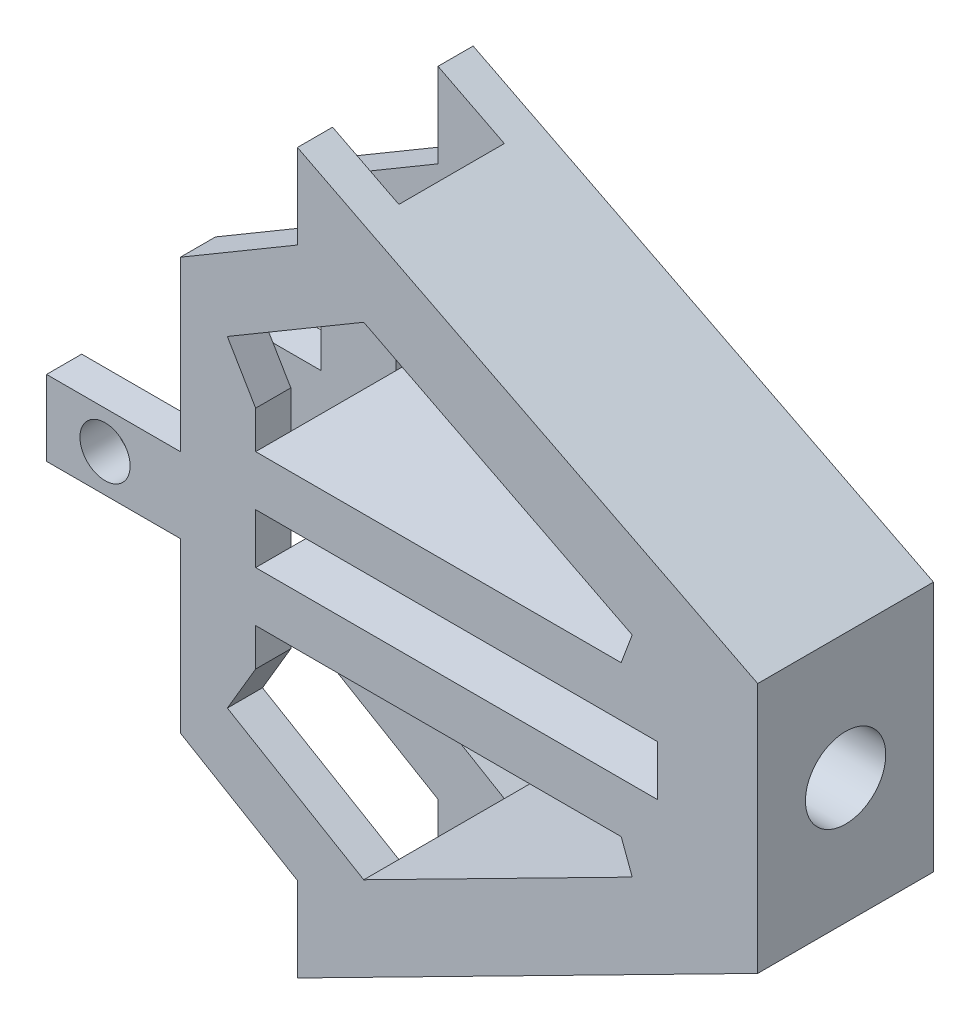
SolidWorks part; units mm, degrees
ref_plane "前视基准面" through (0, 0, 0) normal (0, 0, 1) x (1, 0, 0)
ref_plane "上视基准面" through (0, 0, 0) normal (0, 1, 0) x (1, 0, 0)
ref_plane "右视基准面" through (0, 0, 0) normal (1, 0, 0) x (0, 0, -1)
sketch "草图1" plane through (0, 0, 0) normal (0, 0, 1) x (1, 0, 0)
  line L12 (66, -1) -> (66, 1)
  line L13 (69, -5) -> (40, -19.75)
  line L14 (40, -19.75) -> (37, -19.75)
  line L15 (34.5, -16.75) -> (36.5, -16.75)
  line L16 (31, -16.75) -> (31, -19.75)
  line L17 (34, 13) -> (34, 2.5)
  line L18 (34, 13) -> (31, 16.75)
  line L19 (31, 19.75) -> (34, 19.75)
  line L20 (34, 19.75) -> (34, 17.25)
  line L21 (34.5, 16.75) -> (36.5, 16.75)
  line L22 (37, 13) -> (37, 1.5)
  line L23 (34, -19.75) -> (31, -19.75)
  line L24 (34, -13) -> (31, -16.75)
  line L25 (34, -19.75) -> (34, -17.25)
  line L26 (42.8383, -14.9406) -> (49, -4.5)
  line L27 (46, -1.5) -> (37, -1.5)
  line L28 (34, -2.5) -> (34, -13)
  line L29 (40, 14.6667) -> (46, 4.5)
  line L30 (46, 4.5) -> (46, 1.5)
  line L31 (63, 1.5) -> (64, 4.1774)
  line L32 (49, -1.5) -> (49, -4.5)
  line L33 (49, 4.5) -> (49, 1.5)
  line L34 (49, 1.5) -> (63, 1.5)
  line L35 (37, -17.25) -> (37, -19.75)
  line L36 (37, -1.5) -> (37, -13)
  line L37 (46, -1.5) -> (46, -4.5)
  line L38 (37, 19.75) -> (37, 17.25)
  line L39 (37, -13) -> (40, -14.6667)
  line L40 (46, -4.5) -> (40, -14.6667)
  line L41 (37, 13) -> (40, 14.6667)
  line L42 (37, 1.5) -> (46, 1.5)
  line L43 (42.8383, 14.9406) -> (64, 4.1774)
  line L44 (42.8383, -14.9406) -> (64, -4.1774)
  line L45 (49, 4.5) -> (42.8383, 14.9406)
  line L46 (66.5, 1.5) -> (69, 1.5)
  line L47 (69, 5) -> (69, 1.5)
  line L48 (63, -1.5) -> (49, -1.5)
  line L49 (37, 19.75) -> (40, 19.75)
  line L50 (40, 19.75) -> (69, 5)
  line L51 (31, 19.75) -> (31, 16.75)
  line L52 (69, -5) -> (69, -1.5)
  line L53 (66.5, -1.5) -> (69, -1.5)
  line L54 (63, -1.5) -> (64, -4.1774)
  line L55 (34, -2.5) -> (19.4926, -2.5)
  line L56 (34, 2.5) -> (19.4926, 2.5)
  line L57 (10, -13.9159) -> (19.4926, -2.5)
  line L58 (10, -19.75) -> (10, -13.9159)
  line L59 (10, -19.75) -> (7, -19.75)
  line L60 (7, -17.25) -> (7, -19.75)
  line L61 (3.5, -16.75) -> (6.5, -16.75)
  line L62 (3, -19.75) -> (3, -17.25)
  line L63 (3, -19.75) -> (0, -19.75)
  line L64 (3, -13.75) -> (7, -13.75)
  line L66 (18.0651, 0) -> (7, -13.75)
  line L67 (3, 13.75) -> (7, 13.75)
  line L68 (0, 19.75) -> (3, 19.75)
  line L69 (3, 19.75) -> (3, 17.25)
  line L70 (6.5, 16.75) -> (3.5, 16.75)
  line L71 (7, 19.75) -> (7, 17.25)
  line L72 (7, 19.75) -> (10, 19.75)
  line L73 (19.4926, 2.5) -> (10, 13.9159)
  line L74 (10, 19.75) -> (10, 13.9159)
  line L75 (7, 13.75) -> (18.0651, 0)
  line L78 (0, 19.75) -> (0, -19.75)
  line L81 (3, 13.75) -> (3, -13.75)
  arc A0 (66, -1) -> (66.5, -1.5) centre (66, -1.5) ccw
  arc A1 (37, -17.25) -> (36.5, -16.75) centre (37, -16.75) ccw
  arc A2 (34.5, -16.75) -> (34, -17.25) centre (34, -16.75) ccw
  arc A3 (34, 17.25) -> (34.5, 16.75) centre (34, 16.75) ccw
  arc A4 (36.5, 16.75) -> (37, 17.25) centre (37, 16.75) ccw
  arc A5 (66.5, 1.5) -> (66, 1) centre (66, 1.5) ccw
  arc A6 (7, -17.25) -> (6.5, -16.75) centre (7, -16.75) ccw
  arc A7 (3, 17.25) -> (3.5, 16.75) centre (3, 16.75) ccw
  arc A8 (6.5, 16.75) -> (7, 17.25) centre (7, 16.75) ccw
  arc A9 (3.5, -16.75) -> (3, -17.25) centre (3, -16.75) ccw
extrude "凸台-拉伸1" add sketch "草图1" along normal blind 4
sketch "草图2" plane through (0, -16.75, 0) normal (0, -1, 0) x (1, 0, 0)
  line L0 (3.5, 4) -> (6.5, 4) construction
  line L1 (3, 4) -> (3, 0) construction
  line L2 (7, 4) -> (7, 0) construction
  circle A0 centre (5, 2) radius 0.9
  dimension "D1" = 1.8
  dimension "D2" = 2
  dimension "D3" = 2
  dimension "D4" = 2
extrude "切除-拉伸1" cut sketch "草图2" against normal blind 52
sketch "草图3" plane through (0, 0, 4) normal (0, 0, 1) x (1, 0, 0)
  line L0 (3, 12.413) -> (3, 13.75)
  line L1 (3, 12.413) -> (0, 10.681)
  line L2 (0, 12.681) -> (0, 10.681)
  line L3 (0, 12.681) -> (3, 13.75)
  line L4 (24, -2.5) -> (24, 2.5)
  line L5 (24, -2.5) -> (22, -2.5)
  line L6 (22, 2.5) -> (22, -2.5)
  line L7 (22, 2.5) -> (24, 2.5)
  line L8 (3, -13.75) -> (3, -12.413)
  line L9 (3, -13.75) -> (0, -12.681)
  line L10 (0, -10.681) -> (0, -12.681)
  line L11 (0, -10.681) -> (3, -12.413)
extrude "凸台-拉伸2" add sketch "草图3" along normal blind 1.5
sketch "草图5" plane through (0, 0, 0) normal (0, 0, 1) x (1, 0, 0)
  line L0 (37, 7.25) -> (44.3771, 7.25)
  line L1 (37, 13) -> (37, 1.5) construction
  line L2 (46, 4.5) -> (40, 14.6667) construction
  line L3 (44.3771, 7.25) -> (50.664, 10.9603)
  line L4 (64, 4.1774) -> (42.8383, 14.9406) construction
  line L5 (37, 5.097) -> (45.6477, 5.097)
  line L6 (45.6477, 5.097) -> (53.3059, 9.6166)
  line L8 (42.8383, 14.9406) -> (49, 4.5) construction
  line L9 (37, 5.097) -> (37, 7.25)
  line L10 (53.3059, 9.6166) -> (50.664, 10.9603)
  line L11 (18.0651, 0) -> (31.8024, 0) construction
  line L12 (37, -5.097) -> (45.6477, -5.097)
  line L13 (37, -5.097) -> (37, -7.25)
  line L14 (37, -7.25) -> (44.3771, -7.25)
  line L15 (44.3771, -7.25) -> (50.664, -10.9603)
  line L16 (53.3059, -9.6166) -> (50.664, -10.9603)
  line L17 (45.6477, -5.097) -> (53.3059, -9.6166)
  dimension "D1" = 2.5
  dimension "D2" = 90
extrude "凸台-拉伸3" add sketch "草图5" along normal blind 4
sketch "草图6" plane through (0, 0, 4) normal (0, 0, 1) x (1, 0, 0)
  line L1 (46, 1.5) -> (46, 8.2078)
  line L2 (50.664, 10.9603) -> (50.664, 14.3261)
  line L3 (50.664, 10.9603) -> (46, 8.2078)
  line L4 (69, 5) -> (40, 19.75) construction
  line L10 (37, 0) -> (71.9391, 0) construction
  line L20 (69, 5) -> (50.664, 14.3261)
  line L21 (69, 5) -> (69, -5)
  line L22 (46, 1.5) -> (46, -1.5)
  line L23 (69, -5) -> (50.664, -14.3261)
  line L24 (50.664, -10.9603) -> (50.664, -14.3261)
  line L25 (50.664, -10.9603) -> (46, -8.2078)
  line L26 (46, -1.5) -> (46, -8.2078)
  line L51 (47.8727, 6.4101) -> (49, 4.5)
  line L52 (53.3059, 9.6166) -> (47.8727, 6.4101)
  line L53 (64, 4.1774) -> (53.3059, 9.6166)
  line L54 (63, 1.5) -> (64, 4.1774)
  line L55 (49, 1.5) -> (63, 1.5)
  line L56 (49, 4.5) -> (49, 1.5)
  line L57 (47.8727, 6.4101) -> (49, 4.5)
  line L58 (53.3059, 9.6166) -> (47.8727, 6.4101)
  line L59 (64, 4.1774) -> (53.3059, 9.6166)
  line L60 (63, 1.5) -> (64, 4.1774)
  line L61 (49, 1.5) -> (63, 1.5)
  line L62 (49, 4.5) -> (49, 1.5)
  line L64 (47.8727, -6.4101) -> (53.3059, -9.6166)
  line L65 (49, -4.5) -> (47.8727, -6.4101)
  line L66 (49, -1.5) -> (49, -4.5)
  line L67 (63, -1.5) -> (49, -1.5)
  line L68 (64, -4.1774) -> (63, -1.5)
  line L69 (53.3059, -9.6166) -> (64, -4.1774)
  line L70 (47.8727, -6.4101) -> (53.3059, -9.6166)
  line L71 (49, -4.5) -> (47.8727, -6.4101)
  line L72 (49, -1.5) -> (49, -4.5)
  line L73 (63, -1.5) -> (49, -1.5)
  line L74 (64, -4.1774) -> (63, -1.5)
  line L75 (53.3059, -9.6166) -> (64, -4.1774)
  point P1 (0, 0)
  point P28 (69, 0)
  point P33 (46, 0)
  point P35 (0, 0)
  dimension "D1" = 0
  dimension "D2" = 0
extrude "凸台-拉伸4" add sketch "草图6" along normal blind 1.5
ref_plane "基准面1" through (0, 0, 2) normal (0, 0, 1) x (1, 0, 0)
mirror "镜向1" about plane through (0, 0, 2) normal (0, 0, 1) of "凸台-拉伸4"
sketch "草图7" plane through (0, 0, 2) normal (0, 0, 1) x (1, 0, 0)
  line L0 (53.3059, 9.6166) -> (53.3059, 26.3392)
  line L1 (49, 4.5) -> (49, 1.5) construction
  line L2 (47.8727, 6.4101) -> (49, 4.5) construction
  line L3 (53.3059, 9.6166) -> (47.8727, 6.4101) construction
  line L4 (49, 4.5) -> (49, 1.5)
  line L5 (47.8727, 6.4101) -> (49, 4.5)
  line L6 (53.3059, 9.6166) -> (47.8727, 6.4101)
  line L7 (69, 0) -> (-15.5758, 0) construction
  line L8 (69, -5) -> (69, 5) construction
  line L9 (49, 1.5) -> (49, -1.5)
  line L10 (53.3059, 26.3392) -> (-8.8887, 26.3392)
  line L11 (-8.8887, 26.3392) -> (-8.8887, -26.3392)
  line L12 (53.3059, -26.3392) -> (-8.8887, -26.3392)
  line L13 (53.3059, -9.6166) -> (53.3059, -26.3392)
  line L14 (53.3059, -9.6166) -> (47.8727, -6.4101)
  line L15 (47.8727, -6.4101) -> (49, -4.5)
  line L16 (49, -4.5) -> (49, -1.5)
  point P11 (-15.5758, 0)
  point P15 (-8.8887, 1.5)
  point P16 (0, 0)
  point P18 (-8.8887, 0)
  point P23 (49, 0)
extrude "切除-拉伸2" cut sketch "草图7" against normal mid plane 4
sketch "草图8" plane through (0, 0, 2) normal (0, 0, 1) x (1, 0, 0)
  line L1 (-24.1882, 31.0415) -> (32.5197, 31.0415)
  line L2 (-24.1882, 31.0415) -> (-24.1882, -30.7728)
  line L3 (-24.1882, -30.7728) -> (32.5197, -30.7728)
  line L4 (32.5197, 31.0415) -> (32.5197, -30.7728)
extrude "切除-拉伸3" cut sketch "草图8" along normal blind 10
sketch "草图9" plane through (0, 0, 2) normal (0, 0, 1) x (1, 0, 0)
  line L0 (66.5, -1.5) -> (69, -1.5) construction
  line L1 (66, -1) -> (66, 1) construction
  line L2 (66.5, 1.5) -> (69, 1.5) construction
  line L3 (66.5, -1.5) -> (69, -1.5)
  line L4 (66, -1) -> (66, 1)
  line L5 (66.5, 1.5) -> (69, 1.5)
  line L6 (69, -5) -> (69, 5) construction
  line L7 (69, -1.5) -> (69, 1.5)
  arc A0 (66, -1) -> (66.5, -1.5) centre (66, -1.5) ccw construction
  arc A1 (66.5, 1.5) -> (66, 1) centre (66, 1.5) ccw construction
  arc A2 (66, -1) -> (66.5, -1.5) centre (66, -1.5) ccw
  arc A3 (66.5, 1.5) -> (66, 1) centre (66, 1.5) ccw
extrude "凸台-拉伸5" add sketch "草图9" along normal mid plane 4
sketch "草图10" plane through (69, 0, 0) normal (1, 0, 0) x (0, 0, -1)
  line L0 (1.5, 0) -> (-5.5, 0) construction
  line L1 (1.5, -5) -> (1.5, 5) construction
  line L2 (-5.5, -5) -> (-5.5, 5) construction
  circle A0 centre (-2, 0) radius 1.6
  dimension "D1" = 3.2
sketch "草图11" plane through (0, 0, 2) normal (0, 0, 1) x (1, 0, 0)
  line L0 (50.664, -10.9603) -> (50.664, -14.3261) construction
  line L1 (46, -8.2078) -> (50.664, -10.9603) construction
  line L2 (47.8727, 6.4101) -> (49, 4.5) construction
  line L3 (46, 8.2078) -> (46, -8.2078) construction
  line L4 (50.664, 10.9603) -> (46, 8.2078) construction
  line L5 (69, 5) -> (50.664, 14.3261) construction
  line L6 (50.664, 14.3261) -> (50.664, 10.9603) construction
  line L7 (53.3059, 9.6166) -> (47.8727, 6.4101) construction
  line L8 (50.664, -14.3261) -> (69, -5) construction
  line L9 (47.8727, -6.4101) -> (53.3059, -9.6166) construction
  line L10 (49, -4.5) -> (47.8727, -6.4101) construction
  line L11 (49, -4.5) -> (47.8727, -6.4101)
  line L12 (47.8727, -6.4101) -> (53.3059, -9.6166)
  line L13 (50.664, -14.3261) -> (53.3059, -12.9823)
  line L14 (50.664, -10.9603) -> (50.664, -14.3261)
  line L15 (46, -8.2078) -> (50.664, -10.9603)
  line L16 (47.8727, 6.4101) -> (49, 4.5)
  line L17 (46, 8.2078) -> (46, -8.2078)
  line L18 (50.664, 10.9603) -> (46, 8.2078)
  line L19 (53.3059, 12.9823) -> (50.664, 14.3261)
  line L20 (50.664, 14.3261) -> (50.664, 10.9603)
  line L21 (53.3059, 9.6166) -> (47.8727, 6.4101)
  line L22 (53.3059, 9.6166) -> (53.3059, 12.9823)
  line L23 (53.3059, -9.6166) -> (53.3059, -12.9823)
  line L24 (49, 4.5) -> (49, -4.5)
extrude "切除-拉伸5" cut sketch "草图11" against normal mid plane 4.2
sketch "草图12" plane through (0, 0, 5.5) normal (0, 0, 1) x (1, 0, 0)
  line L0 (43, 0) -> (46, 0) construction
  line L1 (46, 8.2078) -> (46, -8.2078) construction
  line L2 (46, 1.5) -> (40.6702, 1.5)
  line L3 (40.6702, 1.5) -> (40.6702, -1.5)
  line L4 (49, 1.5) -> (63, 1.5) construction
  line L5 (43, 0) -> (40.6702, 0) construction
  line L6 (46, -1.5) -> (40.6702, -1.5)
  line L7 (46, -1.5) -> (46, 1.5)
  circle A0 centre (43, 0) radius 1
  dimension "D1" = 2
  dimension "D2" = 3
extrude "凸台-拉伸6" add sketch "草图12" against normal blind 1.4
mirror "镜向2" about plane through (0, 0, 2) normal (0, 0, 1) of "凸台-拉伸6"
sketch "草图13" plane through (0, 0, 5.5) normal (0, 0, 1) x (1, 0, 0)
  line L0 (69, 0) -> (47.5362, 0) construction
  line L1 (69, -5) -> (69, 5) construction
  line L2 (49, 4.5) -> (49, 1.5) construction
  line L3 (49, 1) -> (65, 1)
  line L4 (49, 1) -> (49, -1)
  line L5 (49, -1) -> (65, -1)
  line L6 (65, 1) -> (65, -1)
  line L7 (49, 1) -> (65, -1) construction
  line L8 (49, -1) -> (65, 1) construction
  point P6 (57, 0)
  dimension "D1" = 2
  dimension "D2" = 4
extrude "切除-拉伸6" cut sketch "草图13" against normal through all
sketch "草图14" plane through (0, 0, 2) normal (0, 0, 1) x (1, 0, 0)
  line L1 (49, 3) -> (63.5603, 3)
  line L2 (40.6702, 0) -> (53.1946, 0) construction
  line L3 (40.6702, 1.5) -> (40.6702, -1.5) construction
  line L4 (49, -3) -> (49, -1.5)
  line L5 (49, -1.5) -> (63, -1.5)
  line L6 (63, -1.5) -> (63.5603, -3)
  line L7 (49, 4.5) -> (49, 1.5)
  line L8 (47.8727, 6.4101) -> (49, 4.5)
  line L9 (53.3059, 9.6166) -> (47.8727, 6.4101)
  line L10 (64, 4.1774) -> (53.3059, 9.6166)
  line L11 (63, 1.5) -> (64, 4.1774)
  line L12 (49, 1.5) -> (63, 1.5)
  line L13 (49, 3) -> (49, 1.5)
  line L17 (63, 1.5) -> (63.5603, 3)
  line L18 (49, 1.5) -> (63, 1.5)
  line L19 (49, -3) -> (63.5603, -3)
  dimension "D2" = 1.5
  dimension "D1" = 0
extrude "凸台-拉伸7" add sketch "草图14" along normal mid plane 7
extrude "切除-拉伸7" cut sketch "草图10" against normal through all contours A0
